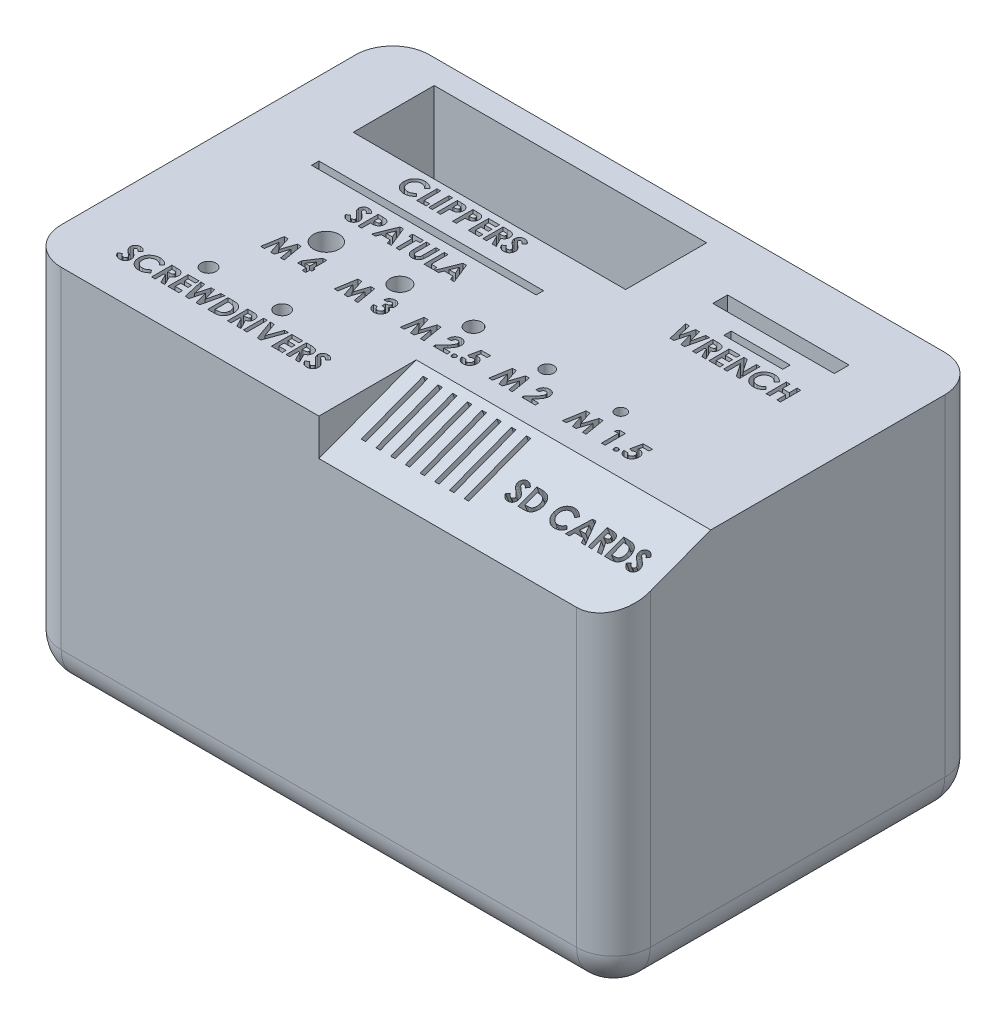
SolidWorks part; units mm, degrees
ref_plane "Front Plane" through (0, 0, 0) normal (0, 0, 1) x (1, 0, 0)
ref_plane "Top Plane" through (0, 0, 0) normal (0, 1, 0) x (1, 0, 0)
ref_plane "Right Plane" through (0, 0, 0) normal (1, 0, 0) x (0, 0, -1)
sketch "Sketch1" plane through (0, 0, 0) normal (0, 1, 0) x (1, 0, 0)
  line L1 (-81.2397, 40.6198) -> (20.3603, 40.6198)
  line L2 (-81.2397, 40.6198) -> (-81.2397, -22.8802)
  line L3 (-81.2397, -22.8802) -> (20.3603, -22.8802)
  line L4 (20.3603, 40.6198) -> (20.3603, -22.8802)
  dimension "D1" = 63.5
  dimension "D2" = 101.6
extrude "Boss-Extrude1" add sketch "Sketch1" along normal blind 63.5
sketch "Sketch2" plane through (0, 63.5, 0) normal (0, 1, 0) x (1, 0, 0)
  line L0 (-81.2397, 40.6198) -> (-81.2397, -22.8802) construction
  line L1 (-68.5397, 15.2198) -> (-29.8047, 15.2198)
  line L2 (-68.5397, 15.2198) -> (-68.5397, 13.9498)
  line L3 (-68.5397, 13.9498) -> (-29.8047, 13.9498)
  line L4 (-29.8047, 15.2198) -> (-29.8047, 13.9498)
  line L5 (20.3603, 40.6198) -> (-81.2397, 40.6198) construction
  dimension "D1" = 1.27
  dimension "D2" = 38.735
  dimension "D3" = 12.7
  dimension "D4" = 25.4
extrude "Cut-Extrude1" cut sketch "Sketch2" against normal blind 50.8
sketch "Sketch3" plane through (0, 63.5, 0) normal (0, 1, 0) x (1, 0, 0)
  line L0 (20.3603, 40.6198) -> (-81.2397, 40.6198) construction
  line L1 (-13.2947, 30.4598) -> (7.6603, 30.4598)
  line L2 (-13.2947, 30.4598) -> (-13.2947, 27.9198)
  line L3 (-13.2947, 27.9198) -> (7.6603, 27.9198)
  line L4 (7.6603, 30.4598) -> (7.6603, 27.9198)
  line L5 (20.3603, -22.8802) -> (20.3603, 40.6198) construction
  line L7 (-7.5797, 25.3798) -> (2.5803, 25.3798)
  line L8 (-7.5797, 25.3798) -> (-7.5797, 24.1098)
  line L9 (-7.5797, 24.1098) -> (2.5803, 24.1098)
  line L10 (2.5803, 25.3798) -> (2.5803, 24.1098)
  point P12 (-2.4997, 25.3798)
  dimension "D1" = 20.955
  dimension "D2" = 2.54
  dimension "D3" = 10.16
  dimension "D4" = 12.7
  dimension "D5" = 10.16
  dimension "D6" = 1.27
  dimension "D7" = 22.86
  dimension "D8" = 15.24
extrude "Cut-Extrude2" cut sketch "Sketch3" against normal blind 50.8
sketch "Sketch4" plane through (0, 63.5, 0) normal (0, 1, 0) x (1, 0, 0)
  line L0 (-81.2397, 40.6198) -> (-81.2397, -22.8802) construction
  line L1 (-81.2397, -22.8802) -> (20.3603, -22.8802) construction
  circle A0 centre (-55.8397, 3.7898) radius 2.2225
  circle A1 centre (-43.1397, 3.7898) radius 1.7145
  circle A2 centre (-30.4397, 3.7898) radius 1.397
  circle A3 centre (-17.7397, 3.7898) radius 1.143
  circle A4 centre (-5.0397, 3.7898) radius 0.9525
  dimension "D1" = 4.445
  dimension "D4" = 12.7
  dimension "D5" = 12.7
  dimension "D6" = 12.7
  dimension "D7" = 12.7
  dimension "D9" = 26.67
  dimension "D10" = 26.67
  dimension "D11" = 26.67
  dimension "D12" = 3.429
  dimension "D13" = 2.794
  dimension "D14" = 2.286
  dimension "D15" = 1.905
  dimension "D2" = 25.4
  dimension "D3" = 26.67
  dimension "D8" = 26.67
extrude "Cut-Extrude3" cut sketch "Sketch4" against normal blind 57.15
sketch "Sketch5" plane through (0, 63.5, 0) normal (0, 1, 0) x (1, 0, 0)
  line L0 (-81.2397, 40.6198) -> (-81.2397, -22.8802) construction
  line L1 (20.3603, 40.6198) -> (-81.2397, 40.6198) construction
  line L2 (-81.2397, -22.8802) -> (20.3603, -22.8802) construction
  text T0 "<b>SPATULA</b>"
  text T1 "<b>WRENCH</b>"
  text T2 "<b>M 1.5</b>\r\n"
  text T3 "<b>M 2</b>"
  text T4 "<b>M 2.5</b>"
  text T5 "<b>M 3</b>"
  text T6 "<b>M 4</b>"
  text T7 "<b>SCREWDRIVERS</b>\r\n"
  text T8 "<b>CLIPPERS</b>"
  dimension "D1" = 68.58
  dimension "D2" = 21.59
  dimension "D3" = 31.75
  dimension "D4" = 22.86
  dimension "D5" = 20.32
  dimension "D6" = 33.02
  dimension "D7" = 44.45
  dimension "D8" = 59.69
  dimension "D9" = 72.39
  dimension "D10" = 20.32
  dimension "D11" = 20.32
  dimension "D12" = 20.32
  dimension "D13" = 20.32
  dimension "D14" = 20.32
  dimension "D15" = 8.89
  dimension "D16" = 6.35
  dimension "D17" = 22.86
  dimension "D18" = 22.86
extrude "Cut-Extrude4" cut sketch "Sketch5" against normal blind 2.54
fillet "Fillet1" radius 6.35 4 edges at (20.3603, 31.75, 22.8802) (20.3603, 31.75, -40.6198) (-81.2397, 31.75, -40.6198) (-81.2397, 31.75, 22.8802)
fillet "Fillet2" radius 6.35 8 edges at (-79.3798, 0, 21.0203) (-81.2397, 0, -8.8698) (-79.3798, 0, -38.76) (-30.4397, 0, -40.6198) (18.5004, 0, -38.76) (20.3603, 0, -8.8698) (18.5004, 0, 21.0203) (-30.4397, 0, 22.8802)
sketch "Sketch6" plane through (0, 63.5, 0) normal (0, 1, 0) x (1, 0, 0)
  line L0 (-81.2397, 34.2698) -> (-81.2397, -16.5302) construction
  line L1 (-74.8897, -22.8802) -> (14.0103, -22.8802) construction
  circle A0 centre (-49.4897, -10.1802) radius 1.27
  circle A1 centre (-62.1897, -10.1802) radius 1.27
  dimension "D1" = 2.54
  dimension "D2" = 2.54
  dimension "D5" = 12.7
  dimension "D6" = 12.7
  dimension "D3" = 31.75
  dimension "D4" = 19.05
extrude "Cut-Extrude5" cut sketch "Sketch6" against normal blind 38.1
sketch "Sketch7" plane through (20.3603, 0, 0) normal (1, 0, 0) x (0, 0, -1)
  line L0 (-6.0952, 63.5) -> (-22.8802, 57.15)
  line L1 (-16.5302, 63.5) -> (34.2698, 63.5) construction
  line L2 (-22.8802, 57.15) -> (-22.8802, 63.5)
  line L3 (-22.8802, 63.5) -> (-6.0952, 63.5)
  line L4 (-22.8802, 6.35) -> (-22.8802, 63.5) construction
  dimension "D1" = 0
  dimension "D2" = 6.35
extrude "Cut-Extrude6" cut sketch "Sketch7" against normal blind 50.8
sketch "Sketch8" plane through (0, 57.5668, 21.7784) normal (0, 0.9353, 0.3538) x (1, 0, 0)
  line L0 (-30.4397, -1.1779) -> (-30.4397, 16.768) construction
  line L1 (-27.8997, 15.3321) -> (-27.1377, 15.3321)
  line L2 (-27.8997, 15.3321) -> (-27.8997, 3.9021)
  line L3 (-27.8997, 3.9021) -> (-27.1377, 3.9021)
  line L4 (-27.1377, 15.3321) -> (-27.1377, 3.9021)
  line L5 (-25.3597, 15.3321) -> (-24.5977, 15.3321)
  line L6 (-25.3597, 15.3321) -> (-25.3597, 3.9021)
  line L7 (-25.3597, 3.9021) -> (-24.5977, 3.9021)
  line L8 (-24.5977, 15.3321) -> (-24.5977, 3.9021)
  line L9 (-22.8197, 15.3321) -> (-22.0577, 15.3321)
  line L10 (-22.8197, 15.3321) -> (-22.8197, 3.9021)
  line L11 (-22.8197, 3.9021) -> (-22.0577, 3.9021)
  line L12 (-22.0577, 15.3321) -> (-22.0577, 3.9021)
  line L13 (-20.2797, 15.3321) -> (-19.5177, 15.3321)
  line L14 (-20.2797, 15.3321) -> (-20.2797, 3.9021)
  line L15 (-20.2797, 3.9021) -> (-19.5177, 3.9021)
  line L16 (-19.5177, 15.3321) -> (-19.5177, 3.9021)
  line L17 (-17.7397, 15.3321) -> (-16.9777, 15.3321)
  line L18 (-17.7397, 15.3321) -> (-17.7397, 3.9021)
  line L19 (-17.7397, 3.9021) -> (-16.9777, 3.9021)
  line L20 (-16.9777, 15.3321) -> (-16.9777, 3.9021)
  line L21 (-15.1997, 15.3321) -> (-14.4377, 15.3321)
  line L22 (-15.1997, 15.3321) -> (-15.1997, 3.9021)
  line L23 (-15.1997, 3.9021) -> (-14.4377, 3.9021)
  line L24 (-14.4377, 15.3321) -> (-14.4377, 3.9021)
  line L25 (-12.6597, 15.3321) -> (-11.8977, 15.3321)
  line L26 (-12.6597, 15.3321) -> (-12.6597, 3.9021)
  line L27 (-12.6597, 3.9021) -> (-11.8977, 3.9021)
  line L28 (-11.8977, 15.3321) -> (-11.8977, 3.9021)
  line L29 (-30.4397, -1.1779) -> (14.0103, -1.1779) construction
  line L31 (-10.1197, 15.3321) -> (-9.3577, 15.3321)
  line L32 (-10.1197, 15.3321) -> (-10.1197, 3.9021)
  line L33 (-10.1197, 3.9021) -> (-9.3577, 3.9021)
  line L34 (-9.3577, 15.3321) -> (-9.3577, 3.9021)
  point P30 (-20.2797, 9.6171)
  dimension "D1" = 11.43
  dimension "D2" = 0.762
  dimension "D3" = 0.762
  dimension "D4" = 11.43
  dimension "D5" = 0.762
  dimension "D6" = 11.43
  dimension "D7" = 2.54
  dimension "D8" = 5.08
  dimension "D9" = 7.62
  dimension "D10" = 10.16
  dimension "D11" = 12.7
  dimension "D12" = 0.762
  dimension "D13" = 11.43
  dimension "D14" = 0.762
  dimension "D15" = 11.43
  dimension "D16" = 5.08
  dimension "D17" = 5.08
  dimension "D18" = 5.08
  dimension "D19" = 5.08
  dimension "D20" = 5.08
  dimension "D21" = 15.24
  dimension "D22" = 5.08
  dimension "D23" = 0.762
  dimension "D24" = 11.43
  dimension "D25" = 17.78
  dimension "D26" = 0.762
  dimension "D27" = 5.08
  dimension "D28" = 11.43
  dimension "D29" = 0.762
  dimension "D30" = 5.08
  dimension "D31" = 11.43
  dimension "D32" = 20.32
extrude "Cut-Extrude7" cut sketch "Sketch8" against normal blind 12.7
sketch "Sketch9" plane through (0, 57.5668, 21.7784) normal (0, 0.9353, 0.3538) x (1, 0, 0)
  line L0 (-30.4397, 16.768) -> (20.3603, 16.768) construction
  line L18 (-30.4397, -1.1779) -> (-30.4397, 16.768) construction
  text T0 "<b>SD CARDS</b>"
  point P5 (-30.4397, 5.7185)
  point P6 (-30.4397, 7.008)
  point P7 (-30.4397, 5.0057)
  dimension "D1" = 10.16
  dimension "D2" = 24.13
extrude "Cut-Extrude8" cut sketch "Sketch9" against normal blind 2.54
sketch "Sketch10" plane through (0, 63.5, 0) normal (0, 1, 0) x (1, 0, 0)
  line L1 (-69.8777, 36.4398) -> (-22.8877, 36.4398)
  line L2 (-69.8777, 36.4398) -> (-69.8777, 22.4698)
  line L3 (-69.8777, 22.4698) -> (-22.8877, 22.4698)
  line L4 (-22.8877, 36.4398) -> (-22.8877, 22.4698)
  dimension "D1" = 46.99
  dimension "D2" = 13.97
extrude "Cut-Extrude9" cut sketch "Sketch10" against normal blind 50.8
